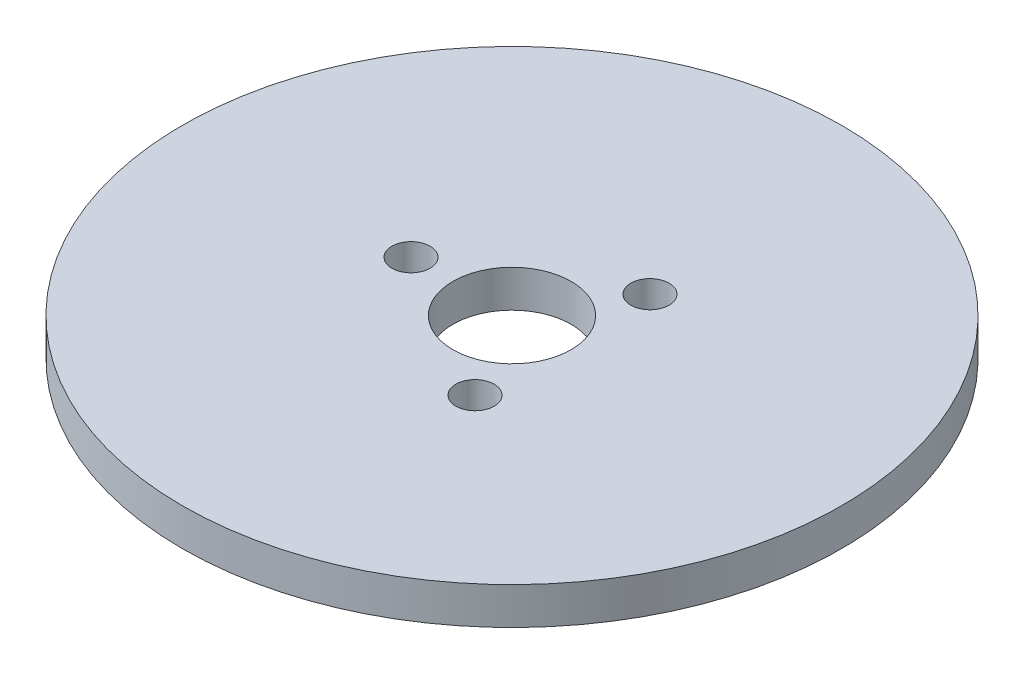
SolidWorks part; units mm, degrees
ref_plane "Front Plane" through (0, 0, 0) normal (0, 0, 1) x (1, 0, 0)
ref_plane "Top Plane" through (0, 0, 0) normal (0, 1, 0) x (1, 0, 0)
ref_plane "Right Plane" through (0, 0, 0) normal (1, 0, 0) x (0, 0, -1)
sketch "Sketch1" plane through (0, 0, 0) normal (0, 1, 0) x (1, 0, 0)
  circle A0 centre (0, 0) radius 97.5
  dimension "FLANGE_OD" = 195
extrude "Boss-Extrude1" add sketch "Sketch1" along normal blind 11
sketch "Sketch2" plane through (0, 0, 0) normal (0, 1, 0) x (1, 0, 0)
  circle A0 centre (0, 0) radius 17.5
  dimension "BORE_D" = 35
extrude "Cut-Extrude1" cut sketch "Sketch2" along normal through all
sketch "Sketch3" plane through (0, 11, 0) normal (0, 1, 0) x (1, 0, 0)
  circle A0 centre (0, 0) radius 29.8766 construction
  circle A1 centre (-29.8766, 0) radius 5.6558
  dimension "BOLT_D" = 11.3117
  dimension "BOLT_PCD" = 59.7533
extrude "Cut-Extrude2" cut sketch "Sketch3" against normal blind 10.1659
pattern_circular "CirPattern1" count 3 over 360 about axis through (0, 0, 0) along (0, 1, 0) of "Cut-Extrude2"
